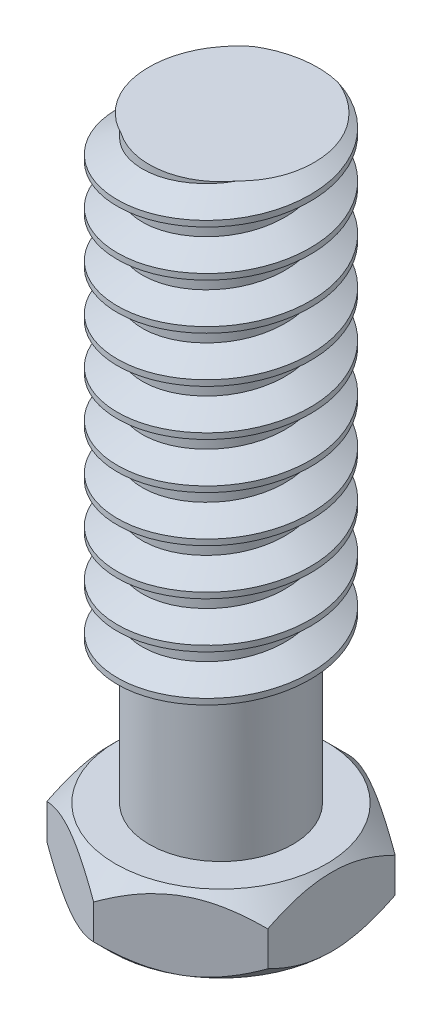
SolidWorks part; units mm, degrees
ref_plane "Front Plane" through (0, 0, 0) normal (0, 0, 1) x (1, 0, 0)
ref_plane "Top Plane" through (0, 0, 0) normal (0, 1, 0) x (1, 0, 0)
ref_plane "Right Plane" through (0, 0, 0) normal (1, 0, 0) x (0, 0, -1)
sketch "Sketch1" plane through (0, 0, 0) normal (0, 1, 0) x (1, 0, 0)
  line L1 (3.0016, -1.7292) -> (2.9984, 1.7349)
  line L2 (2.9984, 1.7349) -> (-0.0033, 3.4641)
  line L3 (-0.0033, 3.4641) -> (-3.0016, 1.7292)
  line L4 (-3.0016, 1.7292) -> (-2.9984, -1.7349)
  line L5 (-2.9984, -1.7349) -> (0.0033, -3.4641)
  line L6 (0.0033, -3.4641) -> (3.0016, -1.7292)
  circle A0 centre (0, 0) radius 3 construction
  dimension "D1" = 6
extrude "Boss-Extrude1" add sketch "Sketch1" along normal blind 2
sketch "Sketch2" plane through (0, 2, 0) normal (0, 1, 0) x (1, 0, 0)
  circle A0 centre (0, 0) radius 1.95
  dimension "D1" = 3.9
extrude "Boss-Extrude2" add sketch "Sketch2" along normal blind 16
thread "Thread1" pitch 1.25 method extrude profile "Thread Profile1" start angle 0, offset 2, length 14, pitch 1.25, diameter 3.9
ref_plane "Plane1" through (-1.95, 20, 0) normal (0, 0, 1) x (-1, 0, 0)
sketch "Thread Profile1" plane through (-1.95, 20, 0) normal (0, 0, 1) x (-1, 0, 0)
  line L0 (0, 0) -> (0, 1.25) construction
  line L1 (0, 0) -> (0.6766, 0.3906)
  line L2 (0.6766, 0.3906) -> (0.6766, 0.5469)
  line L3 (0.6766, 0.5469) -> (0, 0.9375)
  line L4 (0.6766, 0.4687) -> (0, 0.4687) construction
  line L11 (0, 0) -> (0, 0.9375)
  point P2 (0, 0)
  dimension "Pitch" = 1.25
  dimension "Profile_Angle" = 60
  dimension "Profile_Land" = 0.1562
  dimension "Profile_Height" = 0.6766
sketch "Sketch7" plane through (0, 18, 0) normal (0, 1, 0) x (1, 0, 0)
  circle A0 centre (0, 0) radius 4.3418
extrude "Cut-Extrude3" cut sketch "Sketch7" along normal blind 17.5
sketch "Sketch11" plane through (0, 0, 0) normal (0, -1, 0) x (1, 0, 0)
  circle A0 centre (0, 0) radius 3
extrude "Cut-Extrude7" cut sketch "Sketch11" against normal blind 3 draft 45 flip side to cut
sketch "Sketch12" plane through (0, 2, 0) normal (0, 1, 0) x (1, 0, 0)
  circle A0 centre (0, 0) radius 2.8676
extrude "Cut-Extrude8" cut sketch "Sketch12" against normal blind 3 draft 45 flip side to cut
